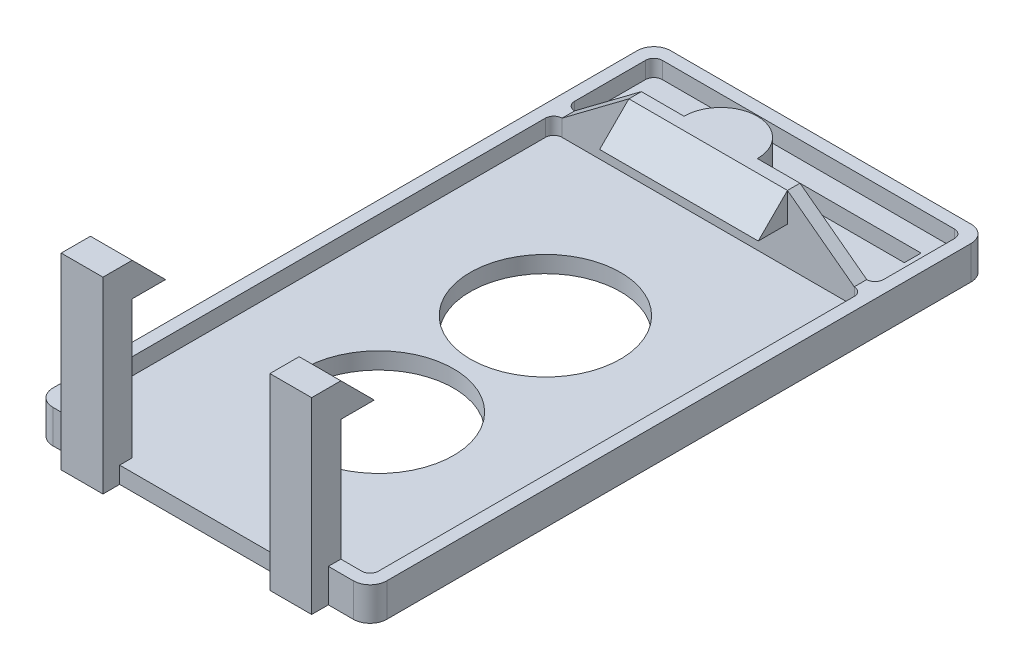
SolidWorks part; units mm, degrees
note: The reader was unsure of these and kept them because the rebuilt part matched: shared geometry of "PCB holder<52>", "PCB holder<55>", "PCB holder<57>", "PCB holder<58>", "Sketch13<3>", "Sketch13<4>".
ref_plane "Front Plane" through (0, 0, 0) normal (0, 0, 1) x (1, 0, 0)
ref_plane "Top Plane" through (0, 0, 0) normal (0, 1, 0) x (1, 0, 0)
ref_plane "Right Plane" through (0, 0, 0) normal (1, 0, 0) x (0, 0, -1)
sketch "PCB holder" plane through (0, 0, 0) normal (0, 1, 0) x (1, 0, 0)
  line L0 (8.75, 14.75) -> (8.75, 21.5)
  line L1 (9, 21.5) -> (-9, 21.5)
  line L2 (10, 20.5) -> (10, -14.5)
  line L3 (9, -15.5) -> (-9, -15.5)
  line L4 (-10, 20.5) -> (-10, -14.5)
  line L5 (-8.75, 14.75) -> (-8.75, 21.5)
  line L7 (8.75, 14.75) -> (-8.75, 14.75)
  line L8 (9.25, 14.25) -> (9.25, -14.25)
  line L9 (8.75, -14.75) -> (-8.75, -14.75)
  line L10 (-9.25, 14.25) -> (-9.25, -14.25)
  line L11 (-8.75, 15.5) -> (8.75, 15.5)
  line L12 (-8.75, 15.5) -> (-8.75, 14.75)
  line L13 (-4.75, 21.5) -> (4.75, 21.5)
  line L14 (-8.75, 14.75) -> (8.75, 14.75)
  line L15 (8.75, 15.5) -> (8.75, 14.75)
  line L17 (-7.5, -14.75) -> (-5, -14.75)
  line L18 (-8.75, 14.75) -> (8.75, 14.75)
  line L20 (-8.75, 21.5) -> (8.75, 21.5)
  line L22 (-7.5, -14.75) -> (-7.5, -16.5)
  line L23 (-7.5, -16.5) -> (-5, -16.5)
  line L24 (-5, -14.75) -> (-5, -16.5)
  line L25 (5, -16.5) -> (7.5, -16.5)
  line L26 (5, -16.5) -> (5, -14.75)
  line L27 (5, -14.75) -> (7.5, -14.75)
  line L28 (7.5, -16.5) -> (7.5, -14.75)
  arc A0 (-9.25, 14.25) -> (-8.75, 14.75) centre (-8.75, 14.25) cw
  arc A1 (9.25, 14.25) -> (8.75, 14.75) centre (8.75, 14.25) ccw
  arc A2 (8.75, -14.75) -> (9.25, -14.25) centre (8.75, -14.25) ccw
  arc A3 (-9.25, -14.25) -> (-8.75, -14.75) centre (-8.75, -14.25) ccw
  arc A4 (-9, 21.5) -> (-10, 20.5) centre (-9, 20.5) ccw
  arc A5 (9, 21.5) -> (10, 20.5) centre (9, 20.5) cw
  arc A6 (-10, -14.5) -> (-9, -15.5) centre (-9, -14.5) ccw
  arc A7 (10, -14.5) -> (9, -15.5) centre (9, -14.5) cw
  circle A12 centre (0, 5) radius 4.5
  circle A13 centre (0, -5) radius 4.5
  point P0 (0, 0)
  point P1 (0, 0)
  point P7 (0, 0)
  line B0 (-8.5, 14.5) -> (8.5, 14.5) construction
  line B1 (-9, 14) -> (-9, -14) construction
  line B2 (-8.5, -14.5) -> (8.5, -14.5) construction
  line B3 (9, 14) -> (9, -14) construction
  arc B4 (-9, 14) -> (-8.5, 14.5) centre (-8.5, 14) cw construction
  arc B5 (9, 14) -> (8.5, 14.5) centre (8.5, 14) ccw construction
  arc B6 (8.5, -14.5) -> (9, -14) centre (8.5, -14) ccw construction
  arc B7 (-9, -14) -> (-8.5, -14.5) centre (-8.5, -14) ccw construction
sketch_block_instance "Block2-1"
sketch_block "Block2"
extrude "Boss-Extrude1" add sketch "PCB holder" along normal blind 1 contours L10 A3 L9 A2 L8 A1 L7 A0 A13 A12 | L2 A7 L3 A6 L4 A4 L1 A5
extrude "Boss-Extrude2" add sketch "PCB holder<52>" along normal blind 1 contours L10 A3 L9 A2 L8 A1 L7 A0 A13 A12
sketch "PCB holder<52>" plane through (0, 0, 0) normal (0, 1, 0) x (1, 0, 0) same geometry as "PCB holder"
extrude "Boss-Extrude3" add sketch "PCB holder<55>" along normal blind 2 contours A7 L2 A5 L1 L0 A1 L8 A2 L9 L28 L3 | L7 L0 L1 L5 | L4 A6 L3 L22 L9 A3 L10 A0 L5 L1 A4
sketch "PCB holder<55>" plane through (0, 0, 0) normal (0, 1, 0) x (1, 0, 0) same geometry as "PCB holder"
extrude "Boss-Extrude7" add sketch "PCB holder<57>" along normal blind 5 contours L11 L5 L7 L0
sketch "PCB holder<57>" plane through (0, 0, 0) normal (0, 1, 0) x (1, 0, 0) same geometry as "PCB holder"
sketch "Sketch6" plane through (0, 0, -14.75) normal (0, 0, 1) x (1, 0, 0)
  line L1 (-4.75, 5) -> (4.75, 5)
  line L2 (-4.75, 5) -> (-4.75, 3.25)
  line L3 (-4.75, 3.25) -> (4.75, 3.25)
  line L4 (4.75, 5) -> (4.75, 3.25)
extrude "Boss-Extrude9" add sketch "Sketch6" along normal blind 1.75
sketch "Sketch7" plane through (4.75, 0, 0) normal (1, 0, 0) x (0, 0, -1)
  line L0 (13, 3.25) -> (14.75, 5)
  line L1 (14.75, 5) -> (13, 5)
  line L2 (13, 5) -> (13, 3.25)
sketch "Sketch8" plane through (0, 0, -14.75) normal (0, 0, 1) x (1, 0, 0)
  line L0 (4.75, 5) -> (8.75, 2)
  line L1 (8.75, 2) -> (8.75, 5)
  line L2 (8.75, 5) -> (4.75, 5)
  line L3 (-4.75, 5) -> (-8.75, 2)
  line L4 (-8.75, 2) -> (-8.75, 5)
  line L5 (-8.75, 5) -> (-4.75, 5)
extrude "Cut-Extrude7" cut sketch "Sketch8" against normal blind 0.75
extrude "Boss-Extrude10" add sketch "PCB holder<58>" along normal blind 11.25 contours L24 L3 L22 L23 | L24 L9 L22 L3 | L25 L28 L3 L26 | L3 L28 L9 L26
sketch "PCB holder<58>" plane through (0, 0, 0) normal (0, 1, 0) x (1, 0, 0) same geometry as "PCB holder"
sketch "Sketch10" plane through (0, 0, 14.75) normal (0, 0, -1) x (-1, 0, 0)
  line L0 (-5, 11.25) -> (-5, 1) construction
  line L1 (-7.5, 11.25) -> (-5, 11.25)
  line L2 (-7.5, 11.25) -> (-7.5, 9.25)
  line L3 (-7.5, 9.25) -> (-5, 9.25)
  line L4 (-5, 11.25) -> (-5, 9.25)
  line L5 (7.5, 11.25) -> (7.5, 2) construction
  line L6 (5, 11.25) -> (7.5, 11.25)
  line L7 (5, 11.25) -> (5, 9.25)
  line L8 (5, 9.25) -> (7.5, 9.25)
  line L9 (7.5, 11.25) -> (7.5, 9.25)
extrude "Boss-Extrude11" add sketch "Sketch10" along normal blind 2
sketch "Sketch11" plane through (7.5, 0, 0) normal (1, 0, 0) x (0, 0, -1)
  line L0 (-14.75, 11.25) -> (-12.75, 9.25)
  line L1 (-16.5, 11.25) -> (-12.75, 11.25) construction
  line L2 (-12.75, 9.25) -> (-12.75, 11.25)
  line L3 (-12.75, 11.25) -> (-12.75, 9.25) construction
  line L4 (-12.75, 11.25) -> (-14.75, 11.25)
extrude "Cut-Extrude8" cut sketch "Sketch11" against normal blind 15
extrude "Cut-Extrude12" cut sketch "Sketch7" against normal blind 9.5 contours L0 L1 L2
sketch "Sketch12" plane through (0, 2, 0) normal (0, 1, 0) x (1, 0, 0)
  line L0 (9.25, 16) -> (9.25, 16.75)
  line L1 (-4.25, 20.75) -> (-8.75, 20.75)
  line L2 (-9.25, 20.25) -> (-9.25, 16)
  line L3 (-8.75, 15.5) -> (8.75, 15.5)
  line L5 (-3, 20.75) -> (8, 20.75) construction
  line L6 (-3, 20.75) -> (-3, 18) construction
  line L7 (-3, 18) -> (8, 18) construction
  line L8 (8, 20.75) -> (8, 18) construction
  line L9 (-3, 20.75) -> (8, 20.75)
  line L10 (-3.75, 20.25) -> (-3.75, 17.75)
  line L11 (-3.25, 17.25) -> (8.75, 17.25)
  line L12 (-3, 20.75) -> (-3, 18)
  line L13 (-3, 18) -> (8, 18)
  line L14 (8, 20.75) -> (8, 18)
  line L15 (-2.5, 20.25) -> (7.5, 20.25)
  line L16 (-2.5, 20.25) -> (-2.5, 18.5)
  line L17 (-2.5, 18.5) -> (7.5, 18.5)
  line L18 (7.5, 20.25) -> (7.5, 18.5)
  arc A0 (8.75, 15.5) -> (9.25, 16) centre (8.75, 16) ccw
  arc A1 (9.25, 16.75) -> (8.75, 17.25) centre (8.75, 16.75) ccw
  arc A2 (-9.25, 20.25) -> (-8.75, 20.75) centre (-8.75, 20.25) cw
  arc A3 (-8.75, 15.5) -> (-9.25, 16) centre (-8.75, 16) cw
  arc A4 (-3.75, 17.75) -> (-3.25, 17.25) centre (-3.25, 17.75) ccw
  arc A5 (-3.75, 20.25) -> (-4.25, 20.75) centre (-4.25, 20.25) ccw
sketch "Sketch13" plane through (0, 2, 0) normal (0, 1, 0) x (1, 0, 0)
  line L1 (-8.75, 20.75) -> (8.75, 20.75)
  line L2 (-9.25, 20.25) -> (-9.25, 16)
  line L3 (-8.75, 15.5) -> (8.75, 15.5)
  line L4 (9.25, 20.25) -> (9.25, 16)
  line L5 (-3, 18.5) -> (8, 18.5)
  line L6 (-3, 18.5) -> (-3, 19.5)
  line L7 (-3, 19.5) -> (8, 19.5)
  line L8 (8, 18.5) -> (8, 19.5)
  arc A0 (8.75, 20.75) -> (9.25, 20.25) centre (8.75, 20.25) cw
  arc A1 (9.25, 16) -> (8.75, 15.5) centre (8.75, 16) cw
  arc A2 (-8.75, 15.5) -> (-9.25, 16) centre (-8.75, 16) cw
  arc A3 (-8.75, 20.75) -> (-9.25, 20.25) centre (-8.75, 20.25) ccw
  arc A4 (2.1975, 15.5) -> (-2.1975, 15.5) centre (0, 15.5) ccw
  line M15 (-8.75, 15.5) -> (8.75, 15.5)
extrude "Cut-Extrude17" cut sketch "Sketch13" against normal blind 1 contours A4 A1 L4 A0 L1 A3 L2 A2 M15 | L5 L8 L7 L6
extrude "Boss-Extrude12" add sketch "Sketch13<3>" along normal blind 3 contours L3 A4
sketch "Sketch13<3>" plane through (0, 2, 0) normal (0, 1, 0) x (1, 0, 0) same geometry as "Sketch13"
extrude "Cut-Extrude18" cut sketch "Sketch13<4>" against normal blind 3 contours L5 L8 L7 L6
sketch "Sketch13<4>" plane through (0, 2, 0) normal (0, 1, 0) x (1, 0, 0) same geometry as "Sketch13"
